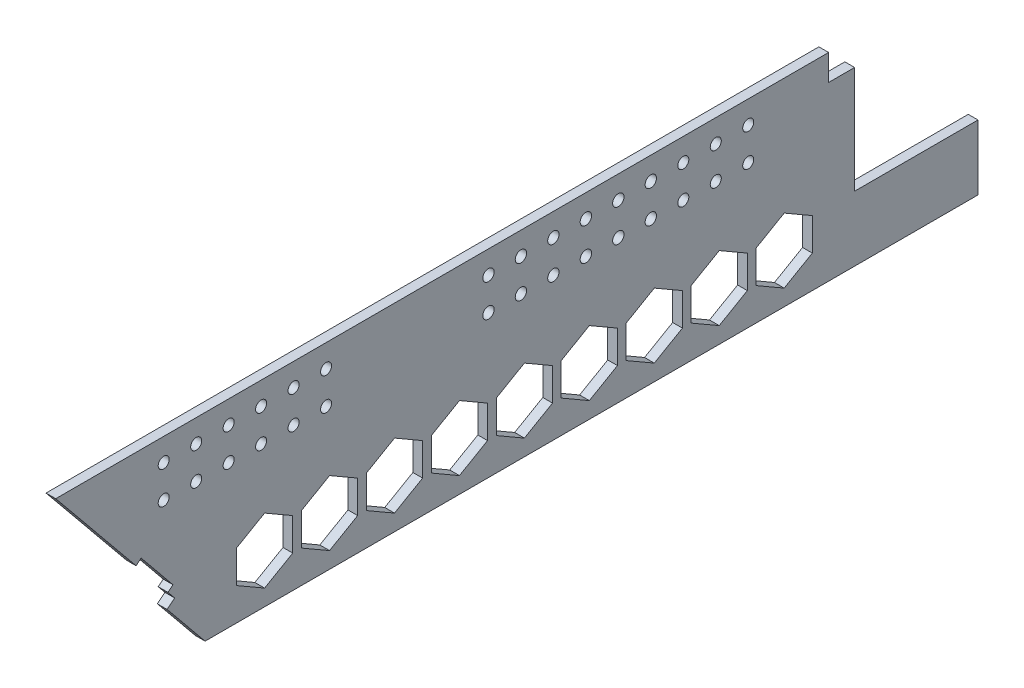
SolidWorks part; units mm, degrees
ref_plane "Front Plane" through (0, 0, 0) normal (0, 0, 1) x (1, 0, 0)
ref_plane "Top Plane" through (0, 0, 0) normal (0, 1, 0) x (1, 0, 0)
ref_plane "Right Plane" through (0, 0, 0) normal (1, 0, 0) x (0, 0, -1)
sketch "Sketch1" plane through (0, 0, 0) normal (0, 0, 1) x (1, 0, 0)
  line L0 (3, 76) -> (3, 0)
  line L2 (0, 0) -> (0, 76)
  line L5 (3, 0) -> (0, 0)
  line L6 (3, 76) -> (0, 76)
  dimension "D1" = 76
  dimension "D2" = 3
extrude "Boss-Extrude1" add sketch "Sketch1" along normal blind 220 contours L2 L0 region at (1.5, 38, 0)
hole_wizard "M3 Clearance Hole1" positions "Sketch2" profile "Sketch3" hole size "M3" standard "ANSI Metric" end condition through all
sketch "Sketch2" plane through (0, 0, 0) normal (-1, 0, 0) x (0, 0, 1)
  point P0 (50.7547, 59)
  point P3 (60.7547, 59)
  point P6 (60.7547, 69)
  point P9 (50.7547, 69)
  point P12 (200.7547, 59)
  point P15 (200.7547, 69)
  point P18 (210.7547, 59)
  point P21 (210.7547, 69)
sketch "Sketch3" plane through (0, 59, 50.7547) normal (0, 1, 0) x (0, 0, 1)
  line L0 (0, 0) -> (0, 3)
  line L1 (0, 3) -> (1.7, 3)
  line L2 (1.7, 3) -> (1.7, 0.025)
  line L3 (1.7, 0.025) -> (1.725, 0)
  line L5 (1.725, 0) -> (0, 0)
  line L6 (-1.7, 0.025) -> (-1.725, 0) construction
  line L11 (0, -6.35) -> (0, 107.95) construction
  dimension "Thru Hole Dia." = 3.4
  dimension "Thru Hole Depth" = 3
  dimension "Near C'Sink Dia." = 3.45
  dimension "Near C'Sink Angle" = 90
sketch "Sketch4" plane through (0, 0, 0) normal (-1, 0, 0) x (0, 0, 1)
  line L0 (220, 0) -> (220, 76) construction
  line L1 (0, 0) -> (220, 0)
  line L2 (0, 0) -> (0, 15)
  line L3 (0, 15) -> (220, 15)
  line L4 (220, 0) -> (220, 15)
  dimension "D1" = 15
extrude "Cut-Extrude1" cut sketch "Sketch4" against normal through all
sketch "Sketch5" plane through (0, 0, 0) normal (-1, 0, 0) x (0, 0, 1)
  line L0 (200.7547, 69) -> (110.7547, 69) construction
  line L2 (110.7547, 69) -> (100.7547, 69) construction
  line L3 (110.7547, 69) -> (110.7547, 59) construction
  line L4 (110.7547, 59) -> (100.7547, 59) construction
  line L5 (100.7547, 69) -> (100.7547, 59) construction
  circle A0 centre (200.7547, 69) radius 1.725 construction
  circle A1 centre (200.7547, 69) radius 1.725 construction
  circle A2 centre (110.7547, 69) radius 1.75
  circle A4 centre (100.7547, 69) radius 1.75
  circle A5 centre (100.7547, 59) radius 1.75
  circle A6 centre (110.7547, 59) radius 1.75
  dimension "D2" = 3.5
  dimension "D1" = 90
  dimension "D3" = 10
  dimension "D4" = 10
extrude "Cut-Extrude2" cut sketch "Sketch5" against normal through all
sketch "Sketch6" plane through (0, 0, 0) normal (-1, 0, 0) x (0, 0, 1)
  circle A0 centre (50.7547, 59) radius 1.725 construction
  circle A1 centre (60.7547, 59) radius 1.7 construction
  circle A2 centre (60.7547, 69) radius 1.725 construction
  circle A3 centre (50.7547, 69) radius 1.725 construction
  circle A4 centre (50.7547, 59) radius 1.725
  circle A5 centre (60.7547, 59) radius 1.7
  circle A6 centre (60.7547, 69) radius 1.725
  circle A7 centre (50.7547, 69) radius 1.725
extrude "Boss-Extrude2" add sketch "Sketch6" against normal blind 3
sketch "Sketch7" plane through (0, 0, 0) normal (-1, 0, 0) x (0, 0, 1)
  line L0 (220, 15) -> (0, 15) construction
  line L1 (220, 76) -> (284, 76)
  line L2 (220, 76) -> (220, 15)
  line L3 (220, 15) -> (238, 15)
  line L5 (249.7101, 29.3221) -> (247.3876, 31.2211)
  line L8 (249.7101, 29.3221) -> (238, 15)
  line L9 (247.3876, 31.2211) -> (249.4448, 33.7371)
  line L10 (249.4448, 33.7371) -> (247.8965, 35.0031)
  line L11 (247.8965, 35.0031) -> (257.7076, 47.0027)
  line L12 (257.7076, 47.0027) -> (259.256, 45.7367)
  line L13 (259.256, 45.7367) -> (284, 76)
  dimension "D1" = 64
  dimension "D2" = 18
  dimension "D3" = 3
  dimension "D4" = 18.5
  dimension "D5" = 2
  dimension "D6" = 3.25
  dimension "D7" = 15.5
extrude "Boss-Extrude3" add sketch "Sketch7" against normal blind 3
sketch "Sketch8" plane through (0, 0, 0) normal (-1, 0, 0) x (0, 0, 1)
  line L0 (284, 76) -> (0, 76) construction
  line L1 (0, 76) -> (46, 76)
  line L4 (46, 76) -> (46, 68)
  line L6 (38, 68) -> (38, 35)
  line L9 (38, 68) -> (46, 68)
  line L10 (0, 76) -> (0, 35)
  line L11 (0, 15) -> (0, 76) construction
  line L12 (0, 35) -> (38, 35)
  dimension "D2" = 46
  dimension "D3" = 8
  dimension "D4" = 8
  dimension "D6" = 33
extrude "Cut-Extrude3" cut sketch "Sketch8" against normal blind 10
pattern_linear "LPattern1" count 3 spacing 20 along (0, 0, 1) of "Cut-Extrude2", "M3 Clearance Hole1"
sketch "Sketch9" plane through (0, 0, 0) normal (-1, 0, 0) x (0, 0, 1)
  line L0 (238, 15) -> (0, 15) construction
  line L1 (59.682, 20) -> (68.3423, 25)
  line L2 (68.3423, 25) -> (68.3423, 35)
  line L3 (68.3423, 35) -> (59.682, 40)
  line L4 (59.682, 40) -> (51.0218, 35)
  line L5 (51.0218, 35) -> (51.0218, 25)
  line L6 (51.0218, 25) -> (59.682, 20)
  line L7 (79.682, 40) -> (71.0218, 35)
  line L8 (71.0218, 25) -> (79.682, 20)
  line L9 (71.0218, 35) -> (71.0218, 25)
  line L10 (88.3423, 25) -> (88.3423, 35)
  line L11 (88.3423, 35) -> (79.682, 40)
  line L12 (79.682, 20) -> (88.3423, 25)
  line L13 (99.682, 40) -> (91.0218, 35)
  line L14 (91.0218, 25) -> (99.682, 20)
  line L15 (91.0218, 35) -> (91.0218, 25)
  line L16 (108.3423, 25) -> (108.3423, 35)
  line L17 (108.3423, 35) -> (99.682, 40)
  line L18 (99.682, 20) -> (108.3423, 25)
  line L19 (119.682, 40) -> (111.0218, 35)
  line L20 (111.0218, 25) -> (119.682, 20)
  line L21 (111.0218, 35) -> (111.0218, 25)
  line L22 (128.3423, 25) -> (128.3423, 35)
  line L23 (128.3423, 35) -> (119.682, 40)
  line L24 (119.682, 20) -> (128.3423, 25)
  line L25 (139.682, 40) -> (131.0218, 35)
  line L26 (131.0218, 25) -> (139.682, 20)
  line L27 (131.0218, 35) -> (131.0218, 25)
  line L28 (148.3423, 25) -> (148.3423, 35)
  line L29 (148.3423, 35) -> (139.682, 40)
  line L30 (139.682, 20) -> (148.3423, 25)
  line L31 (159.682, 40) -> (151.0218, 35)
  line L32 (151.0218, 25) -> (159.682, 20)
  line L33 (151.0218, 35) -> (151.0218, 25)
  line L34 (168.3423, 25) -> (168.3423, 35)
  line L35 (168.3423, 35) -> (159.682, 40)
  line L36 (159.682, 20) -> (168.3423, 25)
  line L37 (179.682, 40) -> (171.0218, 35)
  line L38 (171.0218, 25) -> (179.682, 20)
  line L39 (171.0218, 35) -> (171.0218, 25)
  line L40 (188.3423, 25) -> (188.3423, 35)
  line L41 (188.3423, 35) -> (179.682, 40)
  line L42 (179.682, 20) -> (188.3423, 25)
  line L43 (199.682, 40) -> (191.0218, 35)
  line L44 (191.0218, 25) -> (199.682, 20)
  line L45 (191.0218, 35) -> (191.0218, 25)
  line L46 (208.3423, 25) -> (208.3423, 35)
  line L47 (208.3423, 35) -> (199.682, 40)
  line L48 (199.682, 20) -> (208.3423, 25)
  line L49 (219.682, 40) -> (211.0218, 35)
  line L50 (211.0218, 25) -> (219.682, 20)
  line L51 (211.0218, 35) -> (211.0218, 25)
  line L52 (228.3423, 25) -> (228.3423, 35)
  line L53 (228.3423, 35) -> (219.682, 40)
  line L54 (219.682, 20) -> (228.3423, 25)
  circle A0 centre (59.682, 30) radius 8.6603 construction
  dimension "D1" = 10
  dimension "D2" = 15
  dimension "D3" = 9
extrude "Cut-Extrude4" cut sketch "Sketch9" against normal blind 10
